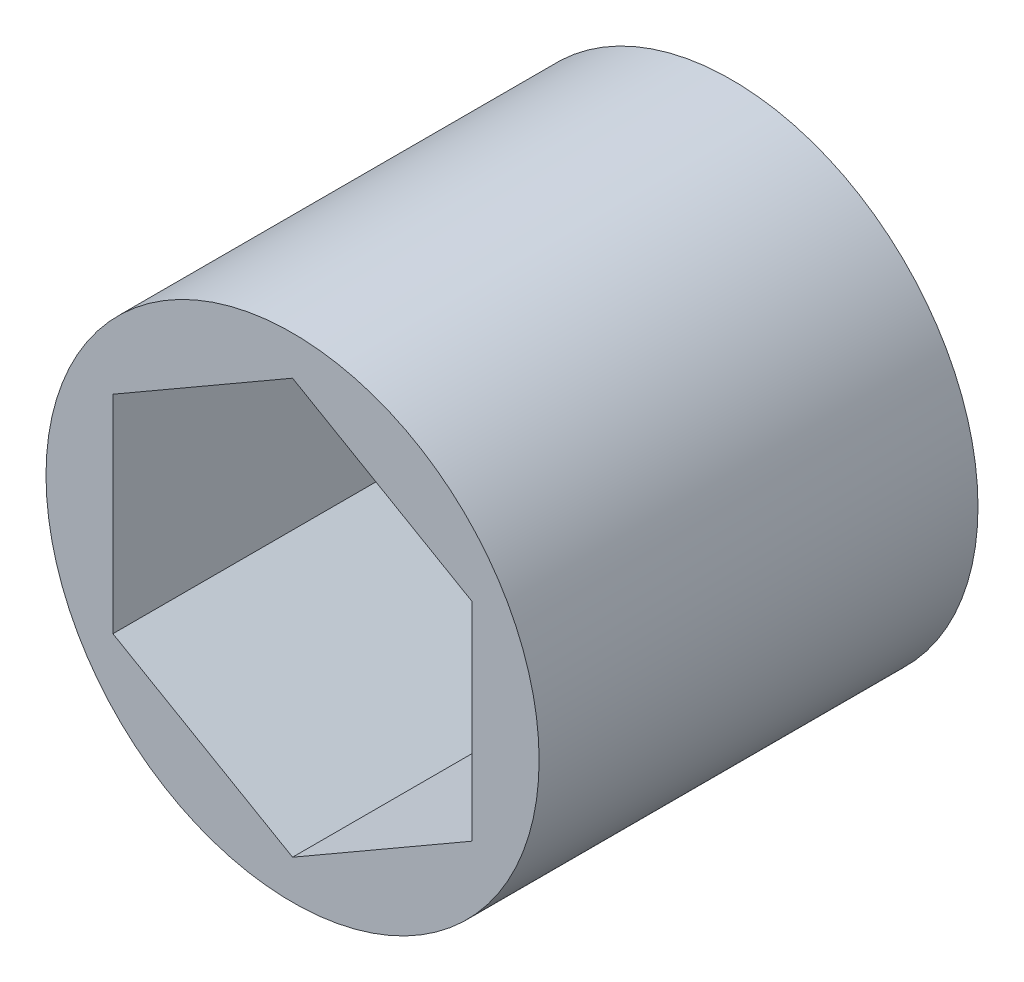
SolidWorks part; units mm, degrees
material "PET"
ref_plane "Front Plane" through (0, 0, 0) normal (0, 0, 1) x (1, 0, 0)
ref_plane "Top Plane" through (0, 0, 0) normal (0, 1, 0) x (1, 0, 0)
ref_plane "Right Plane" through (0, 0, 0) normal (1, 0, 0) x (0, 0, -1)
sketch "Sketch1" plane through (0, 0, 0) normal (0, 0, 1) x (1, 0, 0)
  line L1 (0, 7.479) -> (-6.477, 3.7395)
  line L2 (-6.477, 3.7395) -> (-6.477, -3.7395)
  line L3 (-6.477, -3.7395) -> (0, -7.479)
  line L4 (0, -7.479) -> (6.477, -3.7395)
  line L5 (6.477, -3.7395) -> (6.477, 3.7395)
  line L6 (6.477, 3.7395) -> (0, 7.479)
  circle A0 centre (0, 0) radius 8.89
  circle A1 centre (0, 0) radius 6.477 construction
  dimension "D1" = 12.954
  dimension "D2" = 17.78
extrude "Boss-Extrude1" add sketch "Sketch1" along normal blind 15.8242
